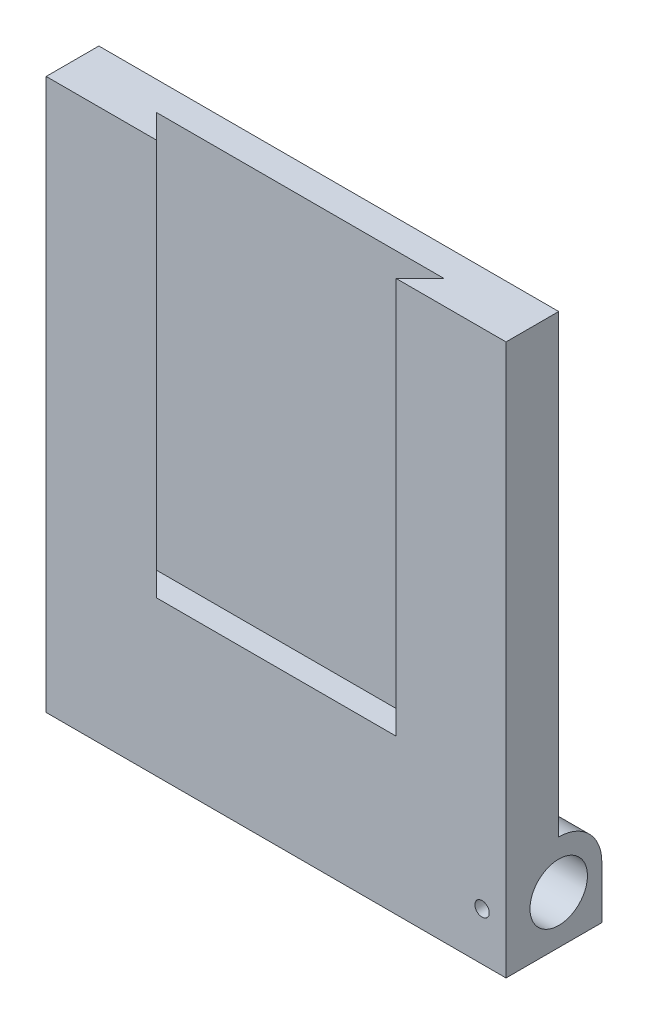
SolidWorks part; units mm, degrees
ref_plane "Front Plane" through (0, 0, 0) normal (0, 0, 1) x (1, 0, 0)
ref_plane "Top Plane" through (0, 0, 0) normal (0, 1, 0) x (1, 0, 0)
ref_plane "Right Plane" through (0, 0, 0) normal (1, 0, 0) x (0, 0, -1)
sketch "Sketch2" plane through (0, 0, 0) normal (0, 1, 0) x (1, 0, 0)
  line L0 (-48, 0) -> (48, 0)
  line L5 (48, 0) -> (48, 20)
  line L6 (48, 20) -> (10, 20)
  line L7 (10, 20) -> (10, 11)
  line L8 (10, 11) -> (-10, 11)
  line L9 (0, 0) -> (0, 11) construction
  line L10 (-48, 20) -> (-10, 20)
  line L11 (-10, 20) -> (-10, 11)
  line L12 (-48, 0) -> (-48, 20)
  point P0 (0, 0)
  dimension "D1" = 96
  dimension "D2" = 11
  dimension "D3" = 9
  dimension "D4" = 20
extrude "Boss-Extrude1" add sketch "Sketch2" along normal blind 10
sketch "Sketch16" plane through (0, 0, 0) normal (0, -1, 0) x (1, 0, 0)
  line L0 (-48, 0) -> (48, 0)
  line L1 (48, 0) -> (48, -20)
  line L2 (48, -20) -> (10, -20)
  line L3 (10, -20) -> (10, -10)
  line L4 (10, -10) -> (-10, -10)
  line L5 (0, -10) -> (0, 0) construction
  line L7 (-48, 0) -> (-48, -20)
  line L8 (-48, -20) -> (-10, -20)
  line L9 (-10, -20) -> (-10, -10)
  dimension "D1" = 10
extrude "Boss-Extrude3" add sketch "Sketch16" along normal blind 10
sketch "Sketch3" plane through (-10, 0, 0) normal (1, 0, 0) x (0, 0, -1)
  line L0 (11, 0) -> (0, 0) construction
  line L3 (11, 0) -> (16.7735, 0) construction
  line L4 (16.7735, 0) -> (13.8868, 5)
  line L5 (13.8868, 5) -> (8.1132, 5)
  line L6 (8.1132, 5) -> (5.2265, 0)
  line L7 (5.2265, 0) -> (8.1132, -5)
  line L8 (8.1132, -5) -> (13.8868, -5)
  line L9 (13.8868, -5) -> (16.7735, 0)
  circle A0 centre (11, 0) radius 5 construction
  dimension "D1" = 10
  dimension "D2" = 11
extrude "Cut-Extrude1" cut sketch "Sketch3" against normal blind 20
sketch "Sketch4" plane through (10, 0, 0) normal (-1, 0, 0) x (0, 0, 1)
  line L0 (-5.2265, 0) -> (0, 0) construction
  line L3 (-11, 0) -> (-5.2265, 0) construction
  line L4 (-16.7735, 0) -> (-13.8868, -5)
  line L5 (-13.8868, -5) -> (-12, -5)
  line L6 (-8.1132, -5) -> (-5.2265, 0)
  line L7 (-5.2265, 0) -> (-8.1132, 5)
  line L8 (-8.1132, 5) -> (-13.8868, 5)
  line L9 (-13.8868, 5) -> (-16.7735, 0)
  line L10 (-12, -5) -> (-12, -10)
  line L11 (-12, -10) -> (-10, -10)
  line L12 (-10, -5) -> (-10, -10)
  line L13 (-10, -5) -> (-8.1132, -5)
  line L14 (-11, 0) -> (-11, -10) construction
  circle A0 centre (-11, 0) radius 5 construction
  point P19 (-11, -10)
  dimension "D1" = 10
  dimension "D2" = 5
  dimension "D3" = 1
  dimension "D4" = 11
extrude "Cut-Extrude2" cut sketch "Sketch4" against normal blind 20
sketch "Sketch5" plane through (30, 0, 0) normal (-1, 0, 0) x (0, 0, 1)
  line L3 (-16.7735, 0) -> (-5.2265, 0) construction
  circle A0 centre (-11, 0) radius 6
  dimension "D1" = 12
extrude "Cut-Extrude3" cut sketch "Sketch5" against normal blind 18
sketch "Sketch11" plane through (0, 10, 0) normal (0, 1, 0) x (1, 0, 0)
  line L0 (48, 0) -> (48, 20) construction
  line L1 (-48, 0) -> (48, 0)
  line L2 (-48, 0) -> (-48, 11)
  line L3 (-48, 11) -> (48, 11)
  line L4 (48, 0) -> (48, 11)
  dimension "D1" = 11
extrude "Boss-Extrude2" add sketch "Sketch11" along normal blind 95
sketch "Sketch14" plane through (-10, 0, 0) normal (1, 0, 0) x (0, 0, -1)
  line L0 (2, 0) -> (10, 0) construction
  line L4 (0, 0) -> (2, 0) construction
  line L6 (11, -9) -> (11, 18)
  line L7 (10, 0) -> (11, 0) construction
  line L9 (3.2058, 4.5) -> (11, 18)
  line L10 (11, 0) -> (11, 18) construction
  arc A3 (3.2058, 4.5) -> (11, -9) centre (11, 0) ccw
  dimension "D2" = 8
  dimension "D1" = 9
  dimension "D5" = 30
  dimension "D3" = 2
  dimension "D4" = 1
extrude "Cut-Extrude10" cut sketch "Sketch14" along normal blind 20
sketch "Sketch17" plane through (0, 105, 0) normal (0, 1, 0) x (1, 0, 0)
  line L0 (25, 0) -> (-25, 0)
  line L1 (-48, 0) -> (48, 0) construction
  line L2 (-25, 0) -> (-30, 5)
  line L3 (-30, 5) -> (30, 5)
  line L4 (0, 0) -> (0, 5) construction
  line L5 (25, 0) -> (30, 5)
  point P5 (0, 0)
  dimension "D1" = 50
  dimension "D2" = 45
  dimension "D3" = 5
extrude "Cut-Extrude11" cut sketch "Sketch17" against normal blind 82.75
fillet "Fillet3" radius 9 2 edges at (29, 10, -20) (-29, 10, -20)
sketch "Sketch18" plane through (0, 0, 0) normal (0, 0, 1) x (1, 0, 0)
  line L0 (48, 0) -> (43, 0) construction
  line L1 (48, 105) -> (48, -10) construction
  circle A0 centre (43, 0) radius 1.5
  dimension "D1" = 3
  dimension "D2" = 5
extrude "Cut-Extrude12" cut sketch "Sketch18" against normal blind 10
